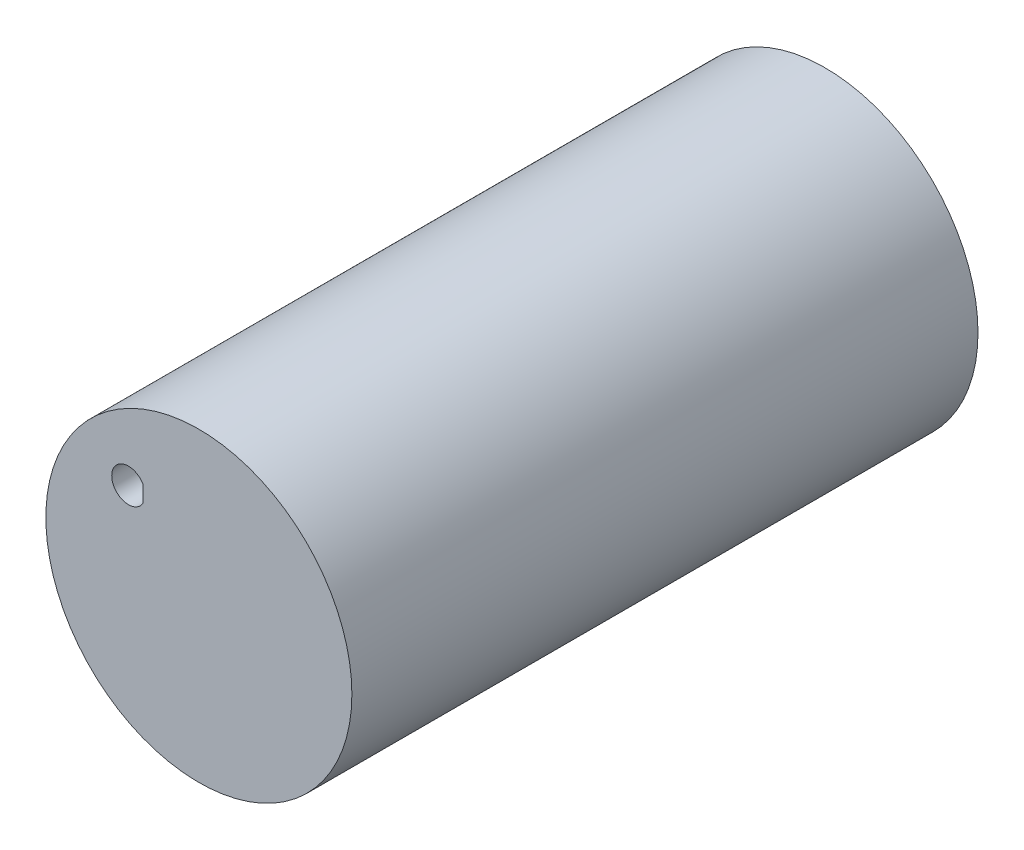
SolidWorks part; units mm, degrees
material "Maple"
ref_plane "Front Plane" through (0, 0, 0) normal (0, 0, 1) x (1, 0, 0)
ref_plane "Top Plane" through (0, 0, 0) normal (0, 1, 0) x (1, 0, 0)
ref_plane "Right Plane" through (0, 0, 0) normal (1, 0, 0) x (0, 0, -1)
curve "Curve3"
  spline degree 3 poles (101.6, 0.1219, 0) (99.9099, 0.5738, 0) (96.5445, 1.4735, 0) (89.7838, 2.9471, 0) (81.3219, 4.3668, 0) (71.1403, 5.4364, 0) (60.9671, 5.9966, 0) (50.8, 6.1452, 0) (40.6357, 5.9983, 0) (30.4708, 5.553, 0) (22.003, 4.9329, 0) (15.2308, 4.2232, 0) (10.9987, 3.6642, 0) (7.608, 3.0922, 0) (5.0721, 2.5808, 0) (2.8944, 1.9709, 0) (1.1817, 1.3642, 0) (-0.6746, 0, 0) (1.1817, -1.3642, 0) (2.8944, -1.9709, 0) (5.0721, -2.5808, 0) (7.608, -3.0922, 0) (10.9987, -3.6642, 0) (15.2308, -4.2232, 0) (22.003, -4.9329, 0) (30.4708, -5.553, 0) (40.6357, -5.9983, 0) (50.8, -6.1452, 0) (60.9671, -5.9966, 0) (71.1403, -5.4364, 0) (81.3219, -4.3668, 0) (89.7838, -2.9471, 0) (96.5445, -1.4735, 0) (99.9099, -0.5738, 0) (101.6, -0.1219, 0) knots 0 0 0 0 0.025456 0.050691 0.100669 0.150236 0.199601 0.248894 0.298185 0.347518 0.396944 0.421725 0.446593 0.459091 0.47168 0.48448 0.49114 0.5 0.50886 0.51552 0.52832 0.540909 0.553407 0.578275 0.603056 0.652482 0.701815 0.751106 0.800399 0.849764 0.899331 0.949309 0.974544 1 1 1 1
sketch "Sketch1" plane through (0, 0, 0) normal (0, 0, 1) x (1, 0, 0)
  line L0 (49.7087, 0.0597) -> (49.7087, -0.0597)
  circle A0 centre (23.4579, 0) radius 29.083
  dimension "D1" = 58.166
extrude "Boss-Extrude1" add sketch "Sketch1" along normal blind 118.999 contours A0 region at (23.4579, 0, 0)
sketch "Sketch2" plane through (0, 0, 118.999) normal (0, 0, 1) x (1, 0, 0)
  line L0 (101.2924, -14.0223) -> (101.2924, -14.2661)
  line L1 (101.6, 0.1219) -> (101.6, -0.1219)
  line L2 (12.5136, 0.5816) -> (12.5136, -2.5934)
  line L3 (40.3437, -14.8199) -> (40.3437, -15.0637)
  line L4 (35.9086, 0.9934) -> (35.9086, -2.1816)
  line L5 (12.8212, 14.7257) -> (12.8212, 11.5507)
  line L6 (105.969, -26.5984) -> (105.969, -26.8422)
  line L7 (17.1902, -11.9945) -> (17.1902, -15.1695)
  arc A0 (12.5136, 0.5816) -> (12.5136, -2.5934) centre (10.0569, -1.0059) ccw
  arc A1 (35.9086, 0.9934) -> (35.9086, -2.1816) centre (33.4519, -0.5941) ccw
  arc A2 (17.1902, -11.9945) -> (17.1902, -15.1695) centre (14.7335, -13.582) ccw
  arc A4 (12.8212, 14.7257) -> (12.8212, 11.5507) centre (10.0716, 13.1382) ccw
  point P15 (12.8212, 13.1382)
  dimension "D1" = 2.925
  dimension "D2" = 2.925
  dimension "D3" = 2.925
  dimension "D6" = 3.175
extrude "Cut-Extrude1" cut sketch "Sketch2" against normal through all contours L5 A4 region at (9.9849, 13.1382, 118.999)
